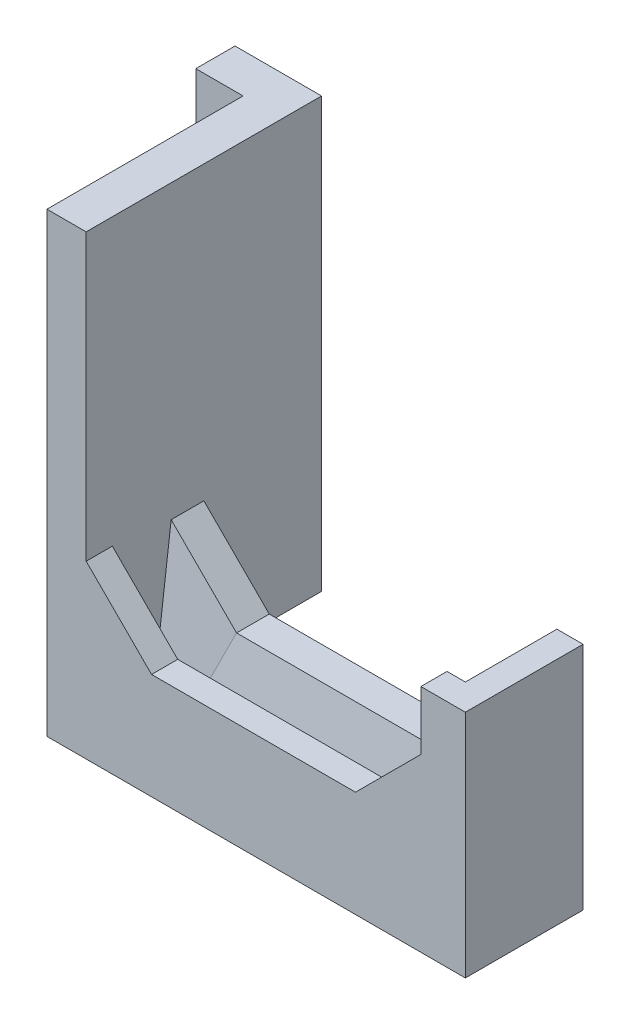
SolidWorks part; units mm, degrees
ref_plane "前视基准面" through (0, 0, 0) normal (0, 0, 1) x (1, 0, 0)
ref_plane "上视基准面" through (0, 0, 0) normal (0, 1, 0) x (1, 0, 0)
ref_plane "右视基准面" through (0, 0, 0) normal (1, 0, 0) x (0, 0, -1)
sketch "草图1" plane through (0, 0, 0) normal (0, 0, 1) x (1, 0, 0)
  line L0 (-25.7629, 88.9526) -> (-25.7629, 78.9526) construction
  line L1 (-22.345, 75.3032) -> (-15.1027, 80.3847)
  line L3 (-30.7629, 88.9526) -> (-30.7629, 78.9526)
  line L4 (-15.1027, 120.5) -> (-15.1027, 64.5) construction
  line L5 (-15.1027, 80.3847) -> (-15.1027, 113.2002)
  line L6 (-15.1027, 118.7) -> (-15.1027, 82.3) construction
  line L7 (-15.1027, 113.2002) -> (-21.719, 113.2002)
  line L8 (-21.719, 113.2002) -> (-21.719, 103.8434)
  line L9 (-25.7629, 99.7995) -> (-29.1745, 99.7995)
  line L10 (-29.1745, 99.7995) -> (-29.1745, 97.1022)
  line L11 (-29.1745, 97.1022) -> (-30.7629, 97.1022)
  line L12 (-30.7629, 97.1022) -> (-30.7629, 88.9526)
  arc A1 (-30.7629, 78.9526) -> (-22.345, 75.3032) centre (-25.7629, 78.9526) ccw
  circle A2 centre (-25.7629, 88.9526) radius 2
  circle A3 centre (-25.7629, 78.9526) radius 2
  arc A4 (-21.719, 103.8434) -> (-25.7629, 99.7995) centre (-25.7629, 103.8434) cw
  point P5 (-25.7629, 83.9526)
  dimension "D1" = 4
extrude "凸台-拉伸1" add sketch "草图1" along normal blind 3
sketch "草图2" plane through (0, 0, 3) normal (0, 0, 1) x (1, 0, 0)
  line L0 (-18.1027, 80.3847) -> (-18.1027, 78.2798)
  line L1 (-15.1027, 113.2002) -> (-18.1027, 113.2002)
  line L2 (-15.1027, 113.2002) -> (-15.1027, 80.3847)
  line L4 (-18.1027, 113.2002) -> (-18.1027, 80.3847)
  line L5 (-22.345, 75.3032) -> (-15.1027, 80.3847) construction
  line L6 (-18.1027, 78.2798) -> (-15.1027, 80.3847)
  dimension "D1" = 3
extrude "凸台-拉伸2" add sketch "草图2" along normal blind 15
sketch "草图3" plane through (-15.1027, 0, 0) normal (1, 0, 0) x (0, 0, -1)
  line L0 (-16, 118.7) -> (-16, 82.3) construction
  line L1 (-18, 80.3847) -> (-16, 80.3847)
  line L2 (-18, 80.3847) -> (-18, 86.3847)
  line L3 (-18, 86.3847) -> (-16, 86.3847)
  line L4 (-16, 80.3847) -> (-16, 86.3847)
extrude "凸台-拉伸3" add sketch "草图3" along normal blind 29
sketch "草图5" plane through (0, 0, 16) normal (0, 0, -1) x (-1, 0, 0)
  line L0 (-11.8973, 82.3) -> (-11.8973, 118.7) construction
  line L1 (-13.8973, 86.3847) -> (-11.8973, 86.3847)
  line L2 (-13.8973, 86.3847) -> (-13.8973, 80.3847)
  line L3 (-13.8973, 80.3847) -> (-11.8973, 80.3847)
  line L4 (-11.8973, 86.3847) -> (-11.8973, 80.3847)
extrude "凸台-拉伸4" add sketch "草图5" along normal blind 7
sketch "草图6" plane through (0, 0, 18) normal (0, 0, 1) x (1, 0, 0)
  line L0 (-18.1027, 78.2798) -> (13.8973, 78.2798)
  line L1 (13.8973, 78.2798) -> (13.8973, 85.2798)
  line L2 (13.8973, 85.2798) -> (-18.1027, 85.2798)
  line L3 (-18.1027, 113.2002) -> (-18.1027, 78.2798) construction
  line L4 (-18.1027, 85.2798) -> (-18.1027, 78.2798)
  dimension "D1" = 7
extrude "凸台-拉伸5" add sketch "草图6" against normal blind 2
chamfer "倒角1" distance 5 angle 45 1 edges at (-15.1027, 86.3847, 17)
sketch "草图8" plane through (0, 0, 16) normal (0, 0, -1) x (-1, 0, 0)
  line L1 (-13.8973, 78.2798) -> (18.1027, 78.2798)
  line L2 (-13.8973, 78.2798) -> (-13.8973, 80.3847)
  line L3 (-13.8973, 80.3847) -> (18.1027, 80.3847)
  line L4 (18.1027, 78.2798) -> (18.1027, 80.3847)
  line L5 (18.1027, 78.2798) -> (-13.8973, 78.2798) construction
extrude "凸台-拉伸6" add sketch "草图8" along normal blind 7
sketch "草图9" plane through (0, 80.3847, 0) normal (0, 1, 0) x (1, 0, 0)
  line L1 (-15.1027, -16) -> (-15.1027, -9) construction
  line L2 (11.8973, -9) -> (-15.1027, -9)
  line L3 (11.8973, -9) -> (11.8973, -13.5)
  line L4 (11.8973, -13.5) -> (-15.1027, -13.5)
  line L5 (-15.1027, -9) -> (-15.1027, -13.5)
  line L6 (-13.3027, -16) -> (10.0973, -16) construction
  dimension "D1" = 2.5
extrude "凸台-拉伸7" add sketch "草图9" along normal blind 5.5
chamfer "倒角2" distance 5 angle 45 1 edges at (-15.1027, 85.8847, 11.25)
sketch "草图10" plane through (0, 86.3847, 0) normal (0, 1, 0) x (1, 0, 0)
  line L1 (11.8973, -9) -> (11.8973, -16)
  line L3 (13.8973, -18) -> (-10.1027, -18) construction
  line L4 (11.8973, -18) -> (13.8973, -18)
  line L5 (13.8973, -18) -> (13.8973, -9)
  line L6 (13.8973, -9) -> (11.8973, -9)
  line L8 (11.8973, -18) -> (10.4941, -18)
  line L9 (10.4941, -18) -> (10.4941, -16)
  line L10 (11.8973, -16) -> (-10.1027, -16) construction
  line L11 (10.4941, -16) -> (11.8973, -16)
extrude "凸台-拉伸8" add sketch "草图10" along normal blind 9.5
chamfer "倒角3" distance 5 angle 45 1 edges at (10.4941, 86.3847, 17)
chamfer "倒角4" distance 3 angle 45 1 edges at (11.8973, 85.8847, 11.25)
chamfer "倒角6" distance 2 angle 80 3 edges at (-12.6027, 88.3847, 13.5) (-0.6027, 85.8847, 13.5) (10.3973, 87.3847, 13.5) first distance on face at (-12.6027, 88.3847, 11.25) first distance on face at (-0.6027, 85.8847, 11.25) first distance on face at (10.3973, 87.3847, 11.25)
